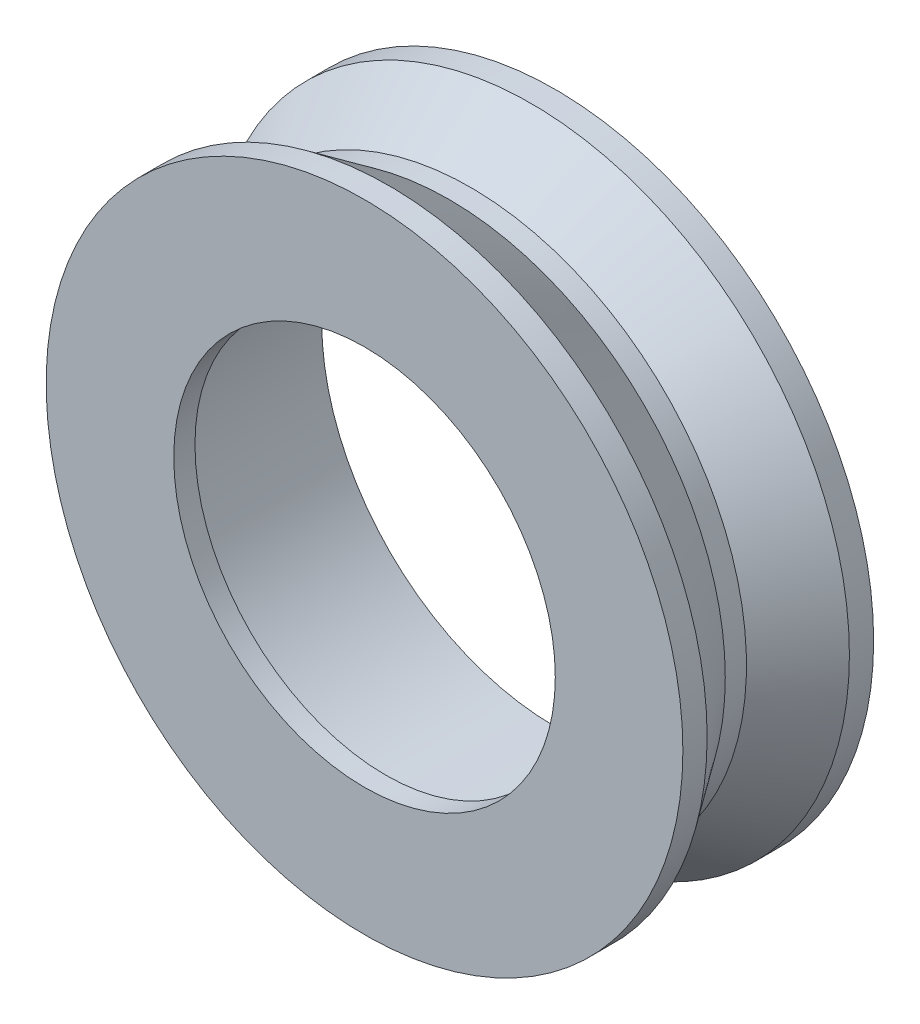
SolidWorks part; units mm, degrees
ref_plane "Front Plane" through (0, 0, 0) normal (0, 0, 1) x (1, 0, 0)
ref_plane "Top Plane" through (0, 0, 0) normal (0, 1, 0) x (1, 0, 0)
ref_plane "Right Plane" through (0, 0, 0) normal (1, 0, 0) x (0, 0, -1)
sketch "Sketch2" plane through (0, 0, 0) normal (0, 0, 1) x (1, 0, 0)
  circle A0 centre (0, 0) radius 11.02
  circle A2 centre (0, 0) radius 13.02
  dimension "D1" = 22.04
  dimension "D2" = 2
extrude "Boss-Extrude1" add sketch "Sketch2" along normal blind 7
sketch "Sketch3" plane through (0, 0, 7) normal (0, 0, 1) x (1, 0, 0)
  circle A0 centre (0, 0) radius 11.02 construction
  circle A1 centre (0, 0) radius 11.02 construction
  circle A2 centre (0, 0) radius 15.02
  circle A3 centre (0, 0) radius 9
  circle A4 centre (0, 0) radius 11.02
  circle M3 centre (0, 0) radius 13.02
  circle M4 centre (0, 0) radius 11.02
  dimension "D2" = 18
  dimension "D1" = 4
extrude "Boss-Extrude2" add sketch "Sketch3" along normal blind 1 contours A2 M3 | A3 M4 | M3 M4 region at (-14.5952, 0, 7) region at (-10.7083, 0, 7) region at (-12.6517, 0, 7)
extrude "Saliente-Extruir1" add sketch "Sketch3<2>" against normal blind 1 from surface contours M3 M4 | A2 M3 region at (-14.5952, 0, 7) region at (-12.6517, 0, 7) starting at face at (13.02, 0, 0)
sketch "Sketch3<2>" plane through (0, 0, 7) normal (0, 0, 1) x (1, 0, 0) same geometry as "Sketch3"
chamfer "Chaflán1" distance 3 angle 35 1 edges at (13.02, 0, 7) first distance on face at (13.02, 0, 7)
chamfer "Chamfer1" distance 3 angle 35 1 edges at (13.02, 0, 0) first distance on face at (13.02, 0, 4)
